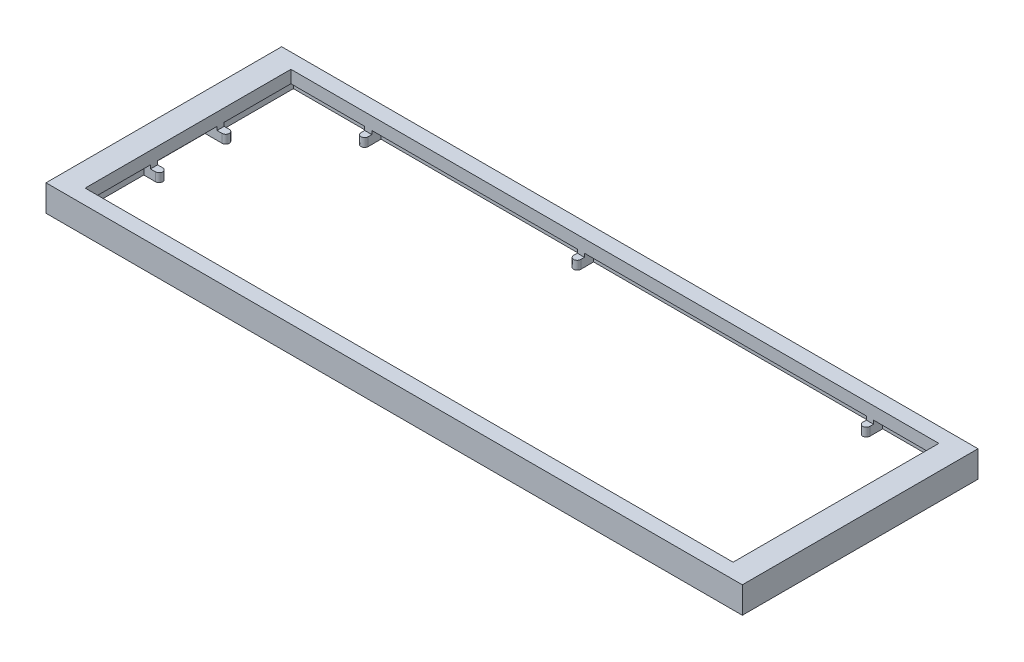
SolidWorks part; units mm, degrees
ref_plane "Front Plane" through (0, 0, 0) normal (0, 0, 1) x (1, 0, 0)
ref_plane "Top Plane" through (0, 0, 0) normal (0, 1, 0) x (1, 0, 0)
ref_plane "Right Plane" through (0, 0, 0) normal (1, 0, 0) x (0, 0, -1)
sketch "Sketch1" plane through (0, 0, 0) normal (0, 1, 0) x (1, 0, 0)
  line L1 (0, 0) -> (390, 0)
  line L2 (0, 0) -> (0, 132)
  line L3 (0, 132) -> (390, 132)
  line L4 (390, 0) -> (390, 132)
  dimension "D1" = 132
  dimension "D2" = 390
extrude "Boss-Extrude1" add sketch "Sketch1" along normal blind 14.8
sketch "Sketch2" plane through (0, 0, 0) normal (0, -1, 0) x (1, 0, 0)
  line L0 (390, -132) -> (0, -132) construction
  line L1 (388, -130) -> (2, -130)
  line L2 (388, -130) -> (388, -2)
  line L3 (388, -2) -> (2, -2)
  line L4 (2, -130) -> (2, -2)
  line L5 (390, 0) -> (390, -132) construction
  point P4 (195, -130)
  point P7 (195, -132)
  point P8 (388, -66)
  point P11 (390, -66)
  dimension "D1" = 2
  dimension "D2" = 2
extrude "Cut-Extrude1" cut sketch "Sketch2" against normal blind 1
sketch "Sketch3" plane through (0, 14.8, 0) normal (0, 1, 0) x (1, 0, 0)
  line L0 (16.55, 120.125) -> (16.55, 107.125) construction
  line L1 (13.55, 123.625) -> (376.45, 123.625)
  line L2 (13.55, 123.625) -> (13.55, 8.375)
  line L3 (13.55, 8.375) -> (376.45, 8.375)
  line L4 (376.45, 123.625) -> (376.45, 8.375)
  line L5 (0, 132) -> (0, 0) construction
  line L6 (390, 132) -> (0, 132) construction
  line L7 (17.05, 120.625) -> (30.05, 120.625) construction
  point P6 (13.55, 66)
  point P9 (0, 66)
  point P10 (195, 123.625)
  point P13 (195, 132)
  dimension "D1" = 3
  dimension "D2" = 3
extrude "Cut-Extrude2" cut sketch "Sketch3" against normal through all
sketch "Sketch4" plane through (0, 1, 0) normal (0, -1, 0) x (-1, 0, 0)
  line L0 (-388, 130) -> (-388, 2) construction
  line L1 (-380.15, 128.7375) -> (-9.85, 128.7375)
  line L2 (-380.15, 128.7375) -> (-380.15, 3.2625)
  line L3 (-380.15, 3.2625) -> (-9.85, 3.2625)
  line L4 (-9.85, 128.7375) -> (-9.85, 3.2625)
  line L6 (-13.55, 123.625) -> (-376.45, 123.625) construction
  line L7 (-379.15, 51.7125) -> (-379.15, 79.5255) construction
  line L9 (-333.1125, 124.7375) -> (-180.7125, 124.7375) construction
  point P4 (-380.15, 66)
  point P7 (-388, 66)
  point P12 (-195, 123.625)
  point P13 (-195, 128.7375)
  dimension "D1" = 1
  dimension "D2" = 4
extrude "Cut-Extrude3" cut sketch "Sketch4" against normal blind 6.8
sketch "Sketch5" plane through (0, 7.8, 0) normal (0, -1, 0) x (1, 0, 0)
  line L0 (13.55, -8.375) -> (376.45, -8.375) construction
  line L1 (380.15, -128.7375) -> (380.15, -3.2625) construction
  line L2 (373.5937, -48.95) -> (380.15, -48.95)
  line L3 (373.5937, -48.95) -> (373.5937, -44.95)
  line L4 (373.5937, -44.95) -> (380.15, -44.95)
  line L5 (380.15, -48.95) -> (380.15, -44.95)
  line L6 (380.15, -3.2625) -> (9.85, -3.2625) construction
  line L7 (301.775, -10.475) -> (297.775, -10.475)
  line L8 (301.775, -10.475) -> (301.775, -3.2625)
  line L9 (301.775, -3.2625) -> (297.775, -3.2625)
  line L10 (297.775, -10.475) -> (297.775, -3.2625)
  line L11 (9.85, -3.2625) -> (9.85, -128.7375) construction
  line L12 (87.4625, -10.475) -> (83.4625, -10.475)
  line L13 (87.4625, -10.475) -> (87.4625, -3.2625)
  line L14 (87.4625, -3.2625) -> (83.4625, -3.2625)
  line L15 (83.4625, -10.475) -> (83.4625, -3.2625)
  line L16 (16.4062, -48.95) -> (9.85, -48.95)
  line L17 (16.4062, -48.95) -> (16.4062, -44.95)
  line L18 (16.4062, -44.95) -> (9.85, -44.95)
  line L19 (9.85, -48.95) -> (9.85, -44.95)
  line L20 (9.85, -128.7375) -> (380.15, -128.7375) construction
  line L21 (16.4062, -86.2562) -> (9.85, -86.2562)
  line L22 (16.4062, -86.2562) -> (16.4062, -82.2562)
  line L23 (16.4062, -82.2562) -> (9.85, -82.2562)
  line L24 (9.85, -86.2562) -> (9.85, -82.2562)
  line L25 (58.8875, -121.5625) -> (54.8875, -121.5625)
  line L26 (58.8875, -121.5625) -> (58.8875, -128.7375)
  line L27 (58.8875, -128.7375) -> (54.8875, -128.7375)
  line L28 (54.8875, -121.5625) -> (54.8875, -128.7375)
  line L30 (177.95, -121.5625) -> (173.95, -121.5625)
  line L31 (177.95, -121.5625) -> (177.95, -128.7375)
  line L32 (177.95, -128.7375) -> (173.95, -128.7375)
  line L33 (173.95, -121.5625) -> (173.95, -128.7375)
  line L34 (339.875, -121.5625) -> (335.875, -121.5625)
  line L35 (339.875, -121.5625) -> (339.875, -128.7375)
  line L36 (339.875, -128.7375) -> (335.875, -128.7375)
  line L37 (335.875, -121.5625) -> (335.875, -128.7375)
  line L38 (373.5937, -86.288) -> (380.15, -86.288)
  line L39 (373.5937, -86.288) -> (373.5937, -82.288)
  line L40 (373.5937, -82.288) -> (380.15, -82.288)
  line L41 (380.15, -86.288) -> (380.15, -82.288)
  line L42 (380.15, -128.7375) -> (380.15, -3.2625) construction
  circle A0 centre (373.5937, -46.95) radius 2
  circle A1 centre (373.5937, -84.288) radius 2
  circle A2 centre (337.875, -121.5625) radius 2
  circle A3 centre (299.775, -10.475) radius 2
  circle A4 centre (85.4625, -10.475) radius 2
  circle A5 centre (16.4062, -46.95) radius 2
  circle A6 centre (175.95, -121.5625) radius 2
  circle A7 centre (56.8875, -121.5625) radius 2
  circle A8 centre (16.4062, -84.2562) radius 2
  arc A9 (16.4062, -86.6375) -> (16.4062, -81.875) centre (16.4062, -84.2562) ccw construction
  arc A10 (16.4062, -49.3312) -> (16.4062, -44.5687) centre (16.4062, -46.95) ccw construction
  arc A11 (59.2687, -121.5625) -> (54.5062, -121.5625) centre (56.8875, -121.5625) ccw construction
  arc A12 (178.3312, -121.5625) -> (173.5687, -121.5625) centre (175.95, -121.5625) ccw construction
  arc A13 (340.2562, -121.5625) -> (335.4937, -121.5625) centre (337.875, -121.5625) ccw construction
  arc A14 (373.5937, -81.9067) -> (373.5937, -86.6692) centre (373.5937, -84.288) ccw construction
  arc A15 (373.5937, -44.5687) -> (373.5937, -49.3312) centre (373.5937, -46.95) ccw construction
  arc A16 (297.3938, -11.2312) -> (302.1562, -11.2312) centre (299.775, -11.2312) ccw construction
  arc A17 (83.0812, -11.2312) -> (87.8437, -11.2312) centre (85.4625, -11.2312) ccw construction
  point P47 (299.775, -13.6125)
  point P52 (85.4625, -13.6125)
  dimension "D2" = 4
  dimension "D1" = 2.1
extrude "Boss-Extrude2" add sketch "Sketch5" along normal up to surface (6.8 mm away) contours L40 L41 L38 L39 | A1 | L4 L5 L2 L3 | A0 | A3 | L8 L9 L10 L7 | L35 L36 L37 L34 | A2 | L33 L32 L31 L30 | A6 | L28 L27 L26 L25 | A7 | L16 L19 L18 L17 | A5 | A8 | L21 L24 L23 L22 | L15 L14 L13 L12 | A4 up to face at (195, 1, -66)
sketch "Sketch6" plane through (0, 7.8, 0) normal (0, 1, 0) x (1, 0, 0)
  line L1 (13.55, 123.625) -> (376.45, 123.625)
  line L2 (13.55, 123.625) -> (13.55, 8.375)
  line L3 (13.55, 8.375) -> (376.45, 8.375)
  line L4 (376.45, 123.625) -> (376.45, 8.375)
extrude "Cut-Extrude4" cut sketch "Sketch6" against normal blind 2
sketch "Sketch7" plane through (0, 1, 0) normal (0, -1, 0) x (-1, 0, 0)
  line L1 (-380.15, 82.288) -> (-383.15, 82.288)
  line L2 (-380.15, 82.288) -> (-380.15, 48.95)
  line L3 (-380.15, 48.95) -> (-383.15, 48.95)
  line L4 (-383.15, 82.288) -> (-383.15, 48.95)
  line L5 (-9.85, 82.2562) -> (-6.85, 82.2562)
  line L6 (-9.85, 82.2562) -> (-9.85, 48.95)
  line L7 (-9.85, 48.95) -> (-6.85, 48.95)
  line L8 (-6.85, 82.2562) -> (-6.85, 48.95)
  line L9 (-16.4062, 48.95) -> (-9.85, 48.95) construction
  line L10 (-373.5937, 48.95) -> (-380.15, 48.95) construction
  dimension "D1" = 3
extrude "Cut-Extrude5" cut sketch "Sketch7" against normal up to surface (6.8 mm away) up to face at (11.7, 7.8, -65.6031)
sketch "Sketch8" plane through (0, 7.8, 0) normal (0, -1, 0) x (-1, 0, 0)
  point P0 (-359.7125, 126.7375)
  point P1 (-381.15, 65.619)
  point P3 (-359.7125, 5.2625)
  point P5 (-241.0375, 5.2625)
  point P7 (-148.9625, 5.2625)
  point P9 (-32.6687, 5.2625)
  point P11 (-8.85, 65.619)
  point P13 (-32.6687, 126.7375)
  point P15 (-102.925, 126.7375)
  point P17 (-195, 126.7375)
  point P19 (-287.075, 126.7375)
hole_wizard "M2x0.4 Tapped Hole1" positions "3DSketch1" profile "Sketch9" tap size "M2x0.4" standard "ANSI Metric"
sketch3d "3DSketch1"
  point P0 (359.7125, 7.8, -126.7375)
  point P3 (381.15, 7.8, -65.619)
  point P6 (359.7125, 7.8, -5.2625)
  point P9 (241.0375, 7.8, -5.2625)
  point P12 (287.075, 7.8, -126.7375)
  point P15 (195, 7.8, -126.7375)
  point P18 (148.9625, 7.8, -5.2625)
  point P21 (102.925, 7.8, -126.7375)
  point P24 (32.6687, 7.8, -126.7375)
  point P27 (8.85, 7.8, -65.619)
  point P30 (32.6687, 7.8, -5.2625)
sketch "Sketch9" plane through (359.7125, 7.8, -126.7375) normal (1, 0, 0) x (0, 0, -1)
  line L0 (0, 0) -> (0, 4.4807)
  line L1 (0, 4.4807) -> (0.8, 4)
  line L2 (0.8, 4) -> (0.8, 0)
  line L5 (0.8, 0) -> (0, 0)
  line L10 (0, 4.4807) -> (-0.8, 4) construction
  line L11 (0, -6.35) -> (0, 107.95) construction
  dimension "Tap Drill Dia." = 1.6
  dimension "Tap Drill Depth" = 4
  dimension "Drill Angle" = 118
cosmetic thread "Hole Thread1" parameters "D1"=4, "D2"=2
cosmetic thread "Hole Thread2" parameters "D1"=4, "D2"=2
cosmetic thread "Hole Thread3" parameters "D1"=4, "D2"=2
cosmetic thread "Hole Thread4" parameters "D1"=4, "D2"=2
cosmetic thread "Hole Thread5" parameters "D1"=4, "D2"=2
cosmetic thread "Hole Thread6" parameters "D1"=4, "D2"=2
cosmetic thread "Hole Thread7" parameters "D1"=4, "D2"=2
cosmetic thread "Hole Thread8" parameters "D1"=4, "D2"=2
cosmetic thread "Hole Thread9" parameters "D1"=4, "D2"=2
cosmetic thread "Hole Thread10" parameters "D1"=4, "D2"=2
cosmetic thread "Hole Thread11" parameters "D1"=4, "D2"=2
